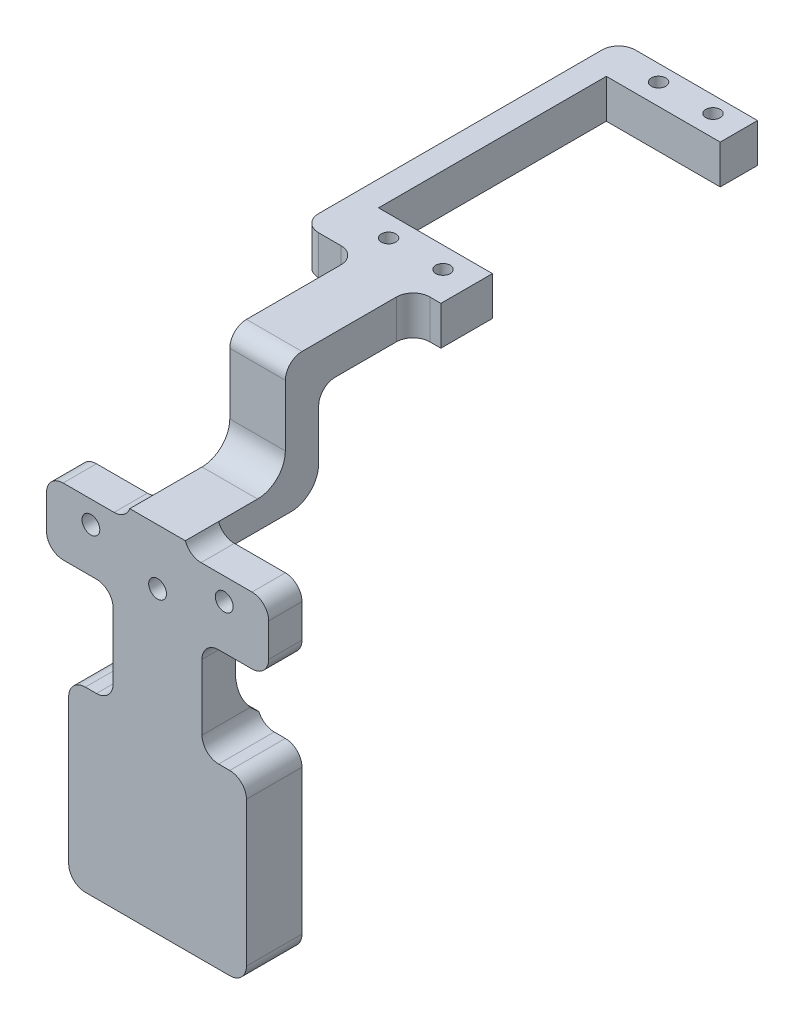
SolidWorks part; units mm, degrees
ref_plane "Front Plane" through (0, 0, 0) normal (0, 0, 1) x (1, 0, 0)
ref_plane "Top Plane" through (0, 0, 0) normal (0, 1, 0) x (1, 0, 0)
ref_plane "Right Plane" through (0, 0, 0) normal (1, 0, 0) x (0, 0, -1)
sketch "Sketch1" plane through (0, 0, 0) normal (0, 0, 1) x (1, 0, 0)
  line L0 (0, 0) -> (0, -151.4897) construction
  line L1 (-13, -85.9078) -> (-8, -85.9078)
  line L2 (-16, -88.9078) -> (-16, -114.9078)
  line L3 (-13, -117.9078) -> (13, -117.9078)
  line L4 (16, -88.9078) -> (16, -114.9078)
  line L6 (0, -101.9078) -> (28.476, -101.9078) construction
  line L9 (-8, -85.9078) -> (-8, -68.0935)
  line L11 (8, -85.9078) -> (8, -68.0935)
  line L12 (8, -85.9078) -> (13, -85.9078)
  line L13 (8, -68.0935) -> (20, -68.0935)
  line L14 (-20, -56.0935) -> (20, -56.0935)
  line L18 (0, -52.2488) -> (-20, -51.3078)
  line L19 (20, -51.3078) -> (0, -52.2488)
  line L20 (20, -68.0935) -> (20, -51.3078)
  line L21 (-20, -68.0935) -> (20, -68.0935)
  line L22 (-20, -51.3078) -> (-20, -68.0935)
  line L25 (20, -68.0935) -> (20, -56.0935)
  line L26 (-20, -68.0935) -> (-8, -68.0935)
  line L27 (-20, -56.0935) -> (-20, -68.0935)
  arc A1 (-16, -114.9078) -> (-13, -117.9078) centre (-13, -114.9078) ccw
  arc A2 (13, -117.9078) -> (16, -114.9078) centre (13, -114.9078) ccw
  arc A3 (13, -85.9078) -> (16, -88.9078) centre (13, -88.9078) cw
  arc A4 (-13, -85.9078) -> (-16, -88.9078) centre (-13, -88.9078) ccw
  point P19 (-16, -117.9078)
  point P22 (16, -117.9078)
  point P25 (16, -85.9078)
  dimension "D1" = 16
  dimension "D5" = 3
  dimension "D2" = 32
  dimension "D3" = 32
  dimension "D4" = 16
  dimension "D6" = 8
  dimension "D7" = 8
  dimension "D8" = 12
  dimension "D9" = 0
extrude "Boss-Extrude1" add sketch "Sketch1" along normal blind 10
sketch "Sketch2" plane through (20, 0, 0) normal (1, 0, 0) x (0, 0, -1)
  line L0 (-4, -56.0935) -> (-4, -75.9441)
  line L1 (-10, -56.0935) -> (0, -56.0935) construction
  line L3 (0, -85.9078) -> (0, -68.0935) construction
  line L4 (-4, -56.0935) -> (0, -56.0935)
  line L5 (0, -56.0935) -> (0, -84.0935)
  arc A0 (0, -84.0935) -> (-4, -75.9441) centre (6.3017, -75.9441) cw
extrude "Cut-Extrude1" cut sketch "Sketch2" against normal up to surface (40 mm away) up to face at (-20, -62.0935, 5)
fillet "Fillet1" radius 3 8 edges at (-8, -68.0935, 7) (-20, -68.0935, 7) (-20, -56.0935, 7) (20, -56.0935, 7) (20, -68.0935, 7) (8, -68.0935, 7) (-8, -85.9078, 5) (8, -85.9078, 5)
sketch "Sketch3" plane through (0, 0, 4) normal (0, 0, -1) x (-1, 0, 0)
  line L0 (-20, -60.0935) -> (20, -60.0935) construction
  line L3 (-20, -59.0935) -> (-20, -65.0935) construction
  line L4 (20, -65.0935) -> (20, -59.0935) construction
  line L5 (17, -56.0935) -> (-17, -56.0935) construction
  line L6 (0, -60.0935) -> (0, -64.0935) construction
  circle A0 centre (-12, -60.0935) radius 1.6
  circle A1 centre (0, -64.0935) radius 1.6
  circle A2 centre (12, -60.0935) radius 1.6
  dimension "D2" = 3.2
  dimension "D3" = 3.2
  dimension "D4" = 12
  dimension "D1" = 4
extrude "Cut-Extrude2" cut sketch "Sketch3" against normal up to surface (6 mm away) up to face at (0, -80.334, 10)
sketch "Sketch4" plane through (0, 0, 0) normal (0, 0, -1) x (-1, 0, 0)
  circle A0 centre (0, -101.9078) radius 16.5 construction
  circle A1 centre (11.6673, -90.2405) radius 1.6 construction
  circle A2 centre (11.6673, -90.2405) radius 1.6
  circle A3 centre (-11.6673, -90.2405) radius 1.6 construction
  circle A4 centre (-11.6673, -90.2405) radius 1.6
  circle A5 centre (-11.6673, -113.575) radius 1.6 construction
  circle A6 centre (-11.6673, -113.575) radius 1.6
  circle A7 centre (11.6673, -113.575) radius 1.6 construction
  circle A8 centre (11.6673, -113.575) radius 1.6
extrude "Cut-Extrude3" cut sketch "Sketch4" against normal blind 7
sketch "Sketch5" plane through (0, 0, 0) normal (1, 0, 0) x (0, 0, -1)
  line L0 (-10, -59.0935) -> (-10, -54.0935)
  line L1 (-10, -51.3078) -> (-10, -68.0935) construction
  line L2 (-10, -54.0935) -> (8, -54.0935)
  line L3 (8, -54.0935) -> (8, -35.0935)
  line L4 (8, -35.0935) -> (88, -35.0935)
  line L5 (88, -35.0935) -> (88, -42.0935)
  line L6 (88, -42.0935) -> (14, -42.0935)
  line L7 (14, -42.0935) -> (14, -59.0935)
  line L8 (14, -59.0935) -> (-10, -59.0935)
  dimension "D1" = 5
  dimension "D2" = 6
  dimension "D3" = 18
  dimension "D4" = 7
  dimension "D5" = 17
  dimension "D6" = 80
extrude "Boss-Extrude2" add sketch "Sketch5" along normal mid plane 10
fillet "Fillet2" radius 3 2 edges at (-5, -56.0935, 7) (5, -56.0935, 7)
fillet "Fillet3" radius 2 1 edges at (0, -59.0935, 4)
fillet "Fillet4" radius 5 2 edges at (0, -54.0935, -8) (0, -59.0935, -14)
fillet "Fillet5" radius 3 2 edges at (0, -35.0935, -8) (0, -42.0935, -14)
sketch "Sketch7" plane through (0, -35.0935, 0) normal (0, 1, 0) x (1, 0, 0)
  line L0 (10, 88) -> (10, 51.1645) construction
  line L1 (10, 88) -> (-15, 88)
  line L2 (10, 88) -> (10, 31)
  line L3 (10, 31) -> (-15, 31)
  line L4 (-15, 88) -> (-15, 31)
  line L5 (10, 88) -> (10, 67.3138) construction
  dimension "D1" = 10
extrude "Boss-Extrude3" add sketch "Sketch7" against normal up to surface (7 mm away) up to face at (0, -42.0935, -52.5)
sketch "Sketch8" plane through (0, -35.0935, 0) normal (0, 1, 0) x (1, 0, 0)
  line L0 (0, 11) -> (0, 88) construction
  line L1 (10.7942, 40.28) -> (10.7942, 81.28)
  line L3 (-5, 11) -> (5, 11) construction
  line L4 (10, 88) -> (-15, 88) construction
  line L6 (-10.5, 81.28) -> (10.7942, 81.28)
  line L7 (-10.5, 81.28) -> (-10.5, 40.28)
  line L8 (-10.5, 40.28) -> (10.7942, 40.28)
  line L10 (-8, 88) -> (8, 88) construction
  line L11 (0, 88) -> (0, 44.5519) construction
  circle A0 centre (-4.9, 85.08) radius 1.3047
  circle A1 centre (4.9, 85.08) radius 1.3047
  circle A2 centre (4.9, 36.48) radius 1.3047
  circle A3 centre (-4.9, 36.48) radius 1.3047
extrude "Cut-Extrude4" cut sketch "Sketch8" against normal up to surface (7 mm away) up to face at (-1.25, -42.0935, -41.75)
fillet "Fillet6" radius 3 4 edges at (-15, -38.5935, -88) (-15, -38.5935, -31) (-5, -38.5935, -31) (5, -38.5935, -31)
